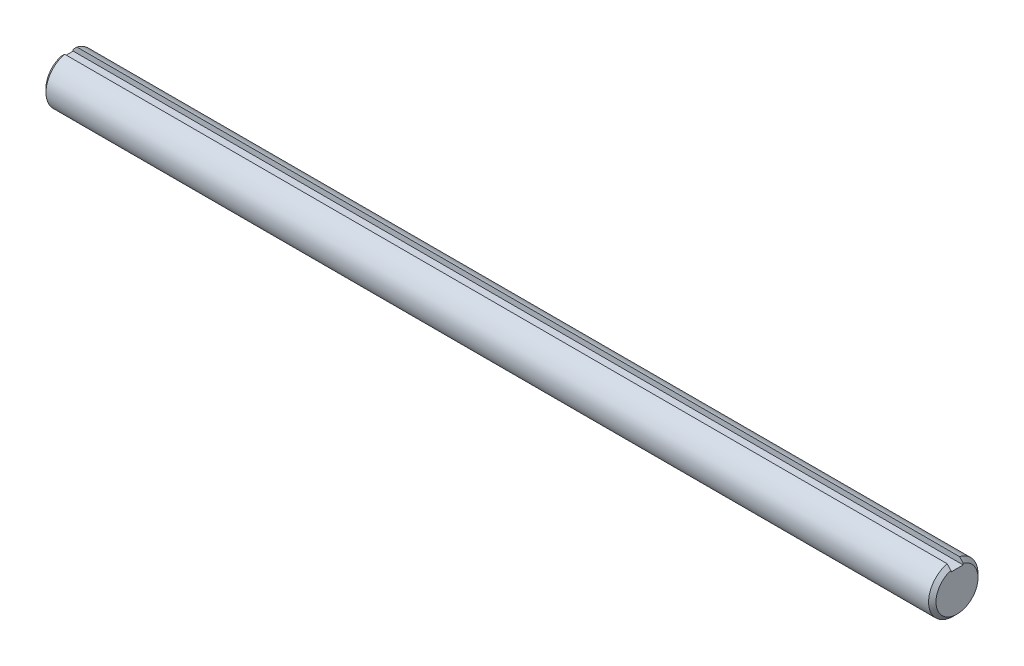
SolidWorks part; units mm, degrees
material "AISI 1045 Steel, cold drawn"
ref_plane "Front" through (0, 0, 0) normal (0, 0, 1) x (1, 0, 0)
ref_plane "Top" through (0, 0, 0) normal (0, 1, 0) x (1, 0, 0)
ref_plane "Right" through (0, 0, 0) normal (1, 0, 0) x (0, 0, -1)
sketch "Sketch1" plane through (0, 0, 0) normal (1, 0, 0) x (0, 0, -1)
  circle A0 centre (0, 0) radius 12.7
  dimension "dia" = 25.4
extrude "Extrude1" add sketch "Sketch1" along normal mid plane 457.2
sketch "Sketch2" plane through (0, 0, 0) normal (0, 0, 1) x (1, 0, 0)
  point P0 (228.6, 12.7)
  point P1 (-228.6, 12.7)
  point P2 (-228.6, -12.7)
chamfer "Chamfer1" distance 1.905 angle 45 2 edges at (-228.6, 0, -12.7) (228.6, 0, -12.7)
sketch "Sketch3" plane through (0, 0, 0) normal (1, 0, 0) x (0, 0, -1)
  line L1 (-3.175, 12.7) -> (3.175, 12.7)
  line L2 (-3.175, 12.7) -> (-3.175, 9.525)
  line L3 (-3.175, 9.525) -> (3.175, 9.525)
  line L4 (3.175, 12.7) -> (3.175, 9.525)
  dimension "key wd" = 6.35
  dimension "key dp" = 3.175
extrude "Extrude2" cut sketch "Sketch3" against normal through all and the other way through all
equation "\"D1@Chamfer1\" = \"dia@Sketch1\" * .075"
